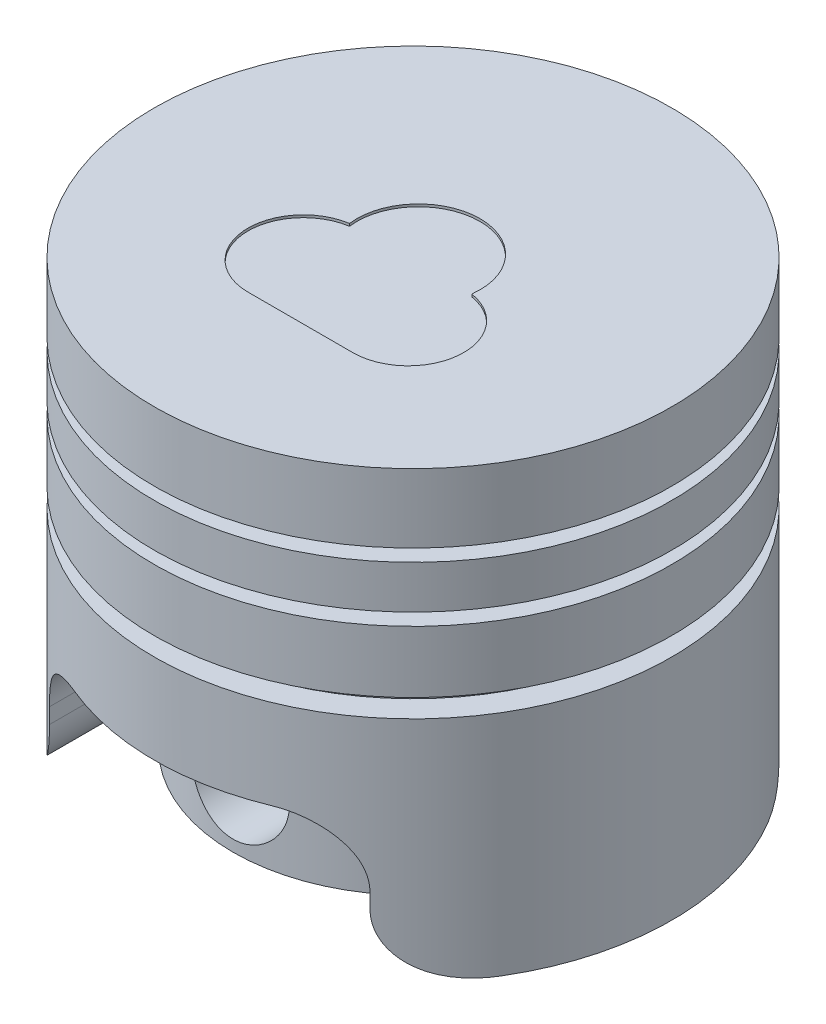
SolidWorks part; units mm, degrees
ref_plane "Front Plane" through (0, 0, 0) normal (0, 0, 1) x (1, 0, 0)
ref_plane "Top Plane" through (0, 0, 0) normal (0, 1, 0) x (1, 0, 0)
ref_plane "Right Plane" through (0, 0, 0) normal (1, 0, 0) x (0, 0, -1)
sketch "Sketch1" plane through (0, 0, 0) normal (0, 0, 1) x (1, 0, 0)
  line L0 (0, 20.16) -> (0, -66.0094) construction
  line L23 (0, 20.16) -> (-42, 20.16)
  line L24 (-42, 20.16) -> (-42, 9)
  line L25 (-42, 9) -> (-38, 9)
  line L26 (-38, 9) -> (-38, 7)
  line L27 (-38, 7) -> (-42, 7)
  line L28 (-42, 7) -> (-42, 0)
  line L29 (-42, 0) -> (-38, 0)
  line L30 (-38, 0) -> (-38, -2)
  line L31 (-38, -2) -> (-42, -2)
  line L32 (-42, -2) -> (-42, -12)
  line L33 (-42, -12) -> (-38, -12)
  line L34 (-38, -12) -> (-38, -15)
  line L35 (-38, -15) -> (-42, -15)
  line L36 (-42, -15) -> (-42, -52)
  line L37 (-42, -52) -> (-29.2, -52)
  line L38 (-29.2, -52) -> (-29.2, 7.16)
  line L39 (-29.2, 7.16) -> (0, 7.16)
  line L40 (0, 7.16) -> (0, 20.16)
  point P2 (-38, 8)
  point P20 (0, 0)
  dimension "D1" = 4
  dimension "D2" = 42
  dimension "D3" = 12.8
  dimension "D4" = 59.16
  dimension "D5" = 13
  dimension "D6" = 3
  dimension "D7" = 10
  dimension "D8" = 2
  dimension "D9" = 7
  dimension "D10" = 2
  dimension "D11" = 37
revolve "Revolve1" add sketch "Sketch1" angle 360 about L0
sketch "Sketch2" plane through (0, 0, 0) normal (0, 0, 1) x (1, 0, 0)
  line L0 (-42, -52) -> (42, -52) construction
  line L1 (-26, -74.5) -> (26, -74.5)
  line L2 (-26, -74.5) -> (-26, -29.5)
  line L3 (-26, -29.5) -> (26, -29.5)
  line L4 (26, -74.5) -> (26, -29.5)
  line L5 (-26, -74.5) -> (26, -29.5) construction
  line L6 (-26, -29.5) -> (26, -74.5) construction
  point P0 (0, -52)
  dimension "D1" = 52
  dimension "D2" = 45
extrude "Cut-Extrude1" cut sketch "Sketch2" against normal through all both and the other way through all
fillet "Fillet1" radius 10 2 edges at (26, -29.5, -23.1377) (26, -29.5, 23.1377)
fillet "Fillet2" radius 10 2 edges at (-26, -29.5, 23.1377) (-26, -29.5, -23.1377)
sketch "Sketch3" plane through (0, 7.16, 0) normal (0, -1, 0) x (1, 0, 0)
  line L0 (25.0527, 15) -> (-25.0527, 15)
  line L2 (25.0527, -15) -> (-25.0527, -15)
  circle A0 centre (0, 0) radius 29.2 construction
  arc A1 (-25.0527, -15) -> (25.0527, -15) centre (0, 0) ccw
  arc A2 (25.0527, 15) -> (-25.0527, 15) centre (0, 0) ccw
extrude "Boss-Extrude1" add sketch "Sketch3" along normal blind 56
sketch "Sketch4" plane through (0, 0, -15) normal (0, 0, 1) x (1, 0, 0)
  circle A0 centre (0, -39) radius 8
  point P2 (0, 0)
  dimension "D1" = 16
  dimension "D2" = 39
extrude "Cut-Extrude2" cut sketch "Sketch4" against normal through all both and the other way through all
fillet "Fillet3" radius 10 2 edges at (26, -52, 23.1377) (-26, -52, 23.1377)
sketch "Sketch5" plane through (0, 20.16, 0) normal (0, 1, 0) x (1, 0, 0)
  line L0 (0, 26.6502) -> (0, -30.3988) construction
  line L1 (-8.5, -18.2716) -> (8.5, -18.2716)
  arc A0 (9.9199, -0.3843) -> (-9.9199, -0.3843) centre (0, 0.8786) ccw
  arc A1 (-9.9199, -0.3843) -> (-8.5, -18.2716) centre (-8.5, -9.2716) ccw
  arc A2 (9.9199, -0.3843) -> (8.5, -18.2716) centre (8.5, -9.2716) cw
  point P9 (0, -18.2716)
  dimension "D2" = 9
  dimension "D3" = 10
  dimension "D1" = 17
extrude "Cut-Extrude3" cut sketch "Sketch5" against normal blind 0.4
